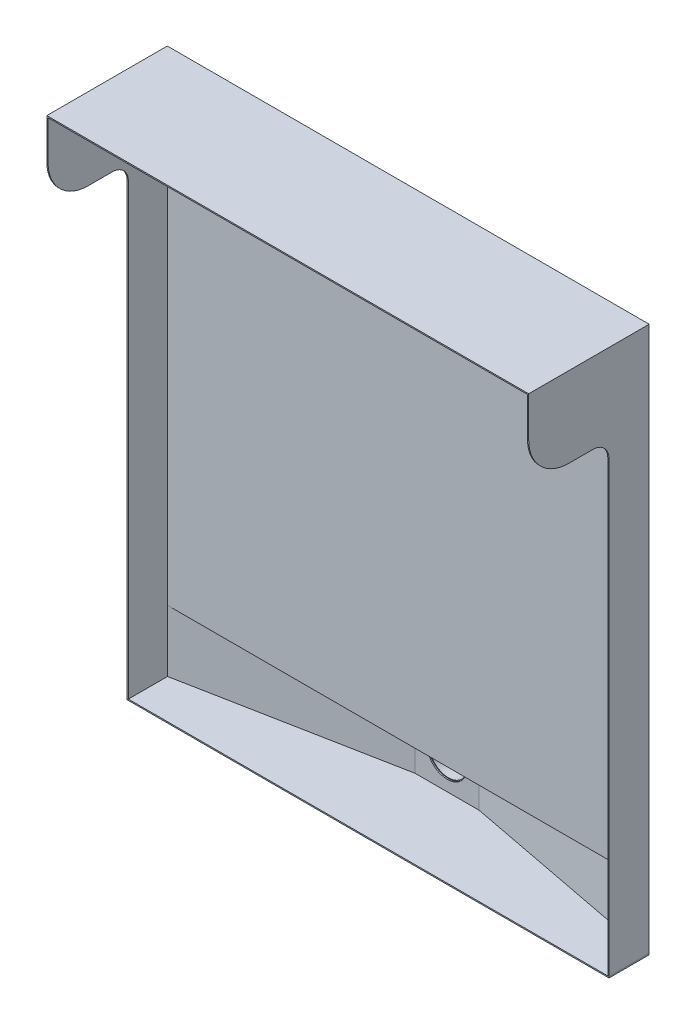
SolidWorks part; units mm, degrees
ref_plane "前视基准面" through (0, 0, 0) normal (0, 0, 1) x (1, 0, 0)
ref_plane "上视基准面" through (0, 0, 0) normal (0, 1, 0) x (1, 0, 0)
ref_plane "右视基准面" through (0, 0, 0) normal (1, 0, 0) x (0, 0, -1)
other "Configuration Table"
sketch "草图6" plane through (0, 0, 0) normal (0, 0, 1) x (1, 0, 0)
  line L1 (300, 340) -> (-300, 340)
  line L2 (300, 340) -> (300, -340)
  line L3 (300, -340) -> (-300, -340)
  line L4 (-300, 340) -> (-300, -340)
  line L5 (300, 340) -> (-300, -340) construction
  line L6 (300, -340) -> (-300, 340) construction
  point P0 (0, 0)
  dimension "D1" = 600
  dimension "D2" = 680
extrude "凸台-拉伸2" add sketch "草图6" along normal blind 150
sketch "草图8" plane through (0, -340, 0) normal (0, -1, 0) x (1, 0, 0)
  line L0 (-300, 0) -> (-40, -50)
  line L3 (40, -50) -> (-40, -50)
  line L5 (0, 0) -> (-40, -50) construction
  line L6 (40, -50) -> (0, 0) construction
  line L7 (40, -50) -> (300, 0)
  line L8 (300, 0) -> (-300, 0)
  point P0 (0, 0)
  dimension "D1" = 50
  dimension "D2" = 80
extrude "凸台-拉伸4" add sketch "草图8" against normal blind 80
shell "抽壳2" thickness 1.5 removed face at (0, 0, 150)
sketch "草图13" plane through (0, 0, -50) normal (0, 0, -1) x (-1, 0, 0)
  circle A0 centre (0, -300) radius 25
  dimension "D1" = 50
extrude "切除-拉伸1" cut sketch "草图13" against normal through all contours A0
split "分割5" bodies to split 113 resulting bodies 124 125 split by face at (0, -338.5, 34.2463)
sketch "草图15" plane through (-300, 0, 0) normal (-1, 0, 0) x (0, 0, 1)
  line L0 (150, 340) -> (0, 340) construction
  line L1 (50, 240) -> (250.7911, 240)
  line L2 (50, 240) -> (50, -426.3886)
  line L3 (50, -426.3886) -> (250.7911, -426.3886)
  line L4 (250.7911, 240) -> (250.7911, -426.3886)
  line L5 (0, 340) -> (0, -260) construction
  dimension "D1" = 100
  dimension "D2" = 50
extrude "切除-拉伸2" cut sketch "草图15" against normal through all contours L2 L1 L4 L3
fillet "圆角1" radius 20 2 edges at (-299.25, 240, 50) (299.25, 240, 50)
fillet "圆角2" radius 50 2 edges at (299.25, 240, 150) (-299.25, 240, 150)
sketch "草图16" plane through (0, 0, -50) normal (0, 0, -1) x (-1, 0, 0)
  circle A3 centre (0, -300) radius 25
  circle A4 centre (0, -300) radius 24
  dimension "D1" = 50
  dimension "D2" = 48
extrude "凸台-拉伸5" add sketch "草图16" along normal blind 25 separate body
sketch "折弯-线28" [suppressed] plane through (0, 0, 0) normal (0, 1, 0) x (1, 0, 0)
sketch "边界框28" [suppressed] plane through (0, 0, 0) normal (0, 1, 0) x (1, 0, 0)
